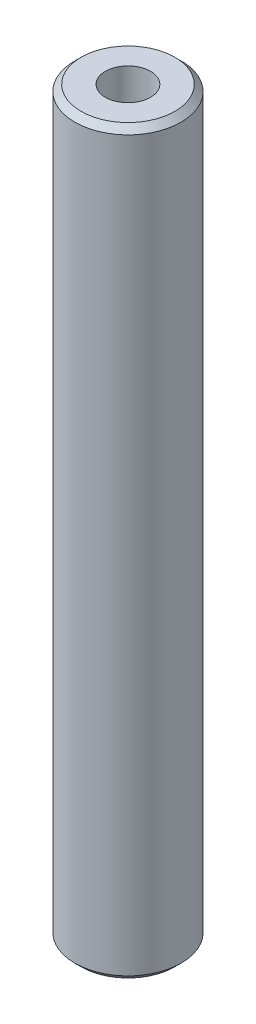
SolidWorks part; units mm, degrees
ref_plane "Front Plane" through (0, 0, 0) normal (0, 0, 1) x (1, 0, 0)
ref_plane "Top Plane" through (0, 0, 0) normal (0, 1, 0) x (1, 0, 0)
ref_plane "Right Plane" through (0, 0, 0) normal (1, 0, 0) x (0, 0, -1)
sketch "Sketch1" plane through (0, 0, 0) normal (0, 1, 0) x (1, 0, 0)
  circle A0 centre (0, 0) radius 7.5
  dimension "SHAFT_OD" = 15
extrude "Boss-Extrude1" add sketch "Sketch1" along normal blind 104.5351
sketch "Sketch2" plane through (0, 0, 0) normal (0, 1, 0) x (1, 0, 0)
  circle A0 centre (0, 0) radius 3.1853
  dimension "BORE_D" = 6.3707
extrude "Cut-Extrude1" cut sketch "Sketch2" along normal through all
chamfer "Chamfer1" distance 0.8818 angle 45 2 edges at (0, 104.5351, 7.5) (0, 0, 7.5)
